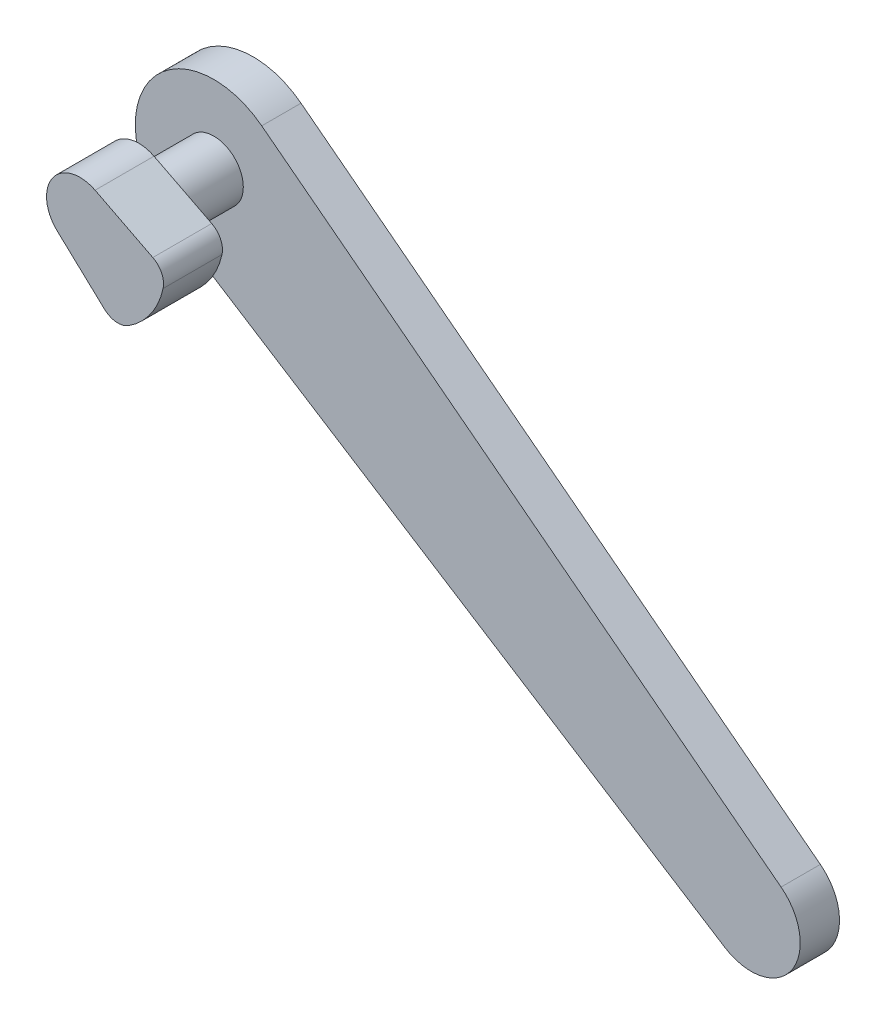
SolidWorks part; units mm, degrees
ref_plane "前视基准面" through (0, 0, 0) normal (0, 0, 1) x (1, 0, 0)
ref_plane "上视基准面" through (0, 0, 0) normal (0, 1, 0) x (1, 0, 0)
ref_plane "右视基准面" through (0, 0, 0) normal (1, 0, 0) x (0, 0, -1)
sketch "草图1" plane through (0, 0, 0) normal (0, 0, 1) x (1, 0, 0)
  line L0 (0.8192, -0.5736) -> (-0.8192, 0.5736) construction
  line L1 (0.8192, -0.5736) -> (3.6313, -2.5427) construction
  line L2 (0.8192, -0.5736) -> (1.4437, -0.5736) construction
  line L3 (-1.9785, -0.6697) -> (0.4349, -2.9203)
  line L4 (-0.0474, 2.0883) -> (2.893, 0.5901)
  line L5 (0, 0) -> (0, 2.9589) construction
  line L6 (0, 0) -> (3.4373, 0) construction
  line L7 (0, 0) -> (0, 3.4623) construction
  arc A0 (-0.0474, 2.0883) -> (-1.9785, -0.6697) centre (-0.8192, 0.5736) ccw
  arc A1 (0.4349, -2.9203) -> (1.6529, -3.0332) centre (1.1169, -2.189) ccw
  arc A2 (1.6529, -3.0332) -> (3.4156, -0.5158) centre (-0.491, 0.3438) ccw
  arc A3 (2.893, 0.5901) -> (3.4156, -0.5158) centre (2.439, -0.3009) cw
  circle A4 centre (0, 0) radius 1.5
  dimension "D4" = 4
  dimension "D5" = 1
  dimension "D7" = 3
  dimension "D8" = 1.7
  dimension "D1" = 35
  dimension "D2" = 2
  dimension "D3" = 8
  dimension "D6" = 3.3
extrude "凸台-拉伸1" add sketch "草图1" along normal blind 3 contours A4 | A3 L4 A0 L3 A1 A2 A4 region at (-2.1455, 1.5023, 0) region at (0, 0, 0)
extrude "凸台-拉伸2" add sketch "草图1<3>" against normal blind 3 contours A4 region at (0, 0, 0)
sketch "草图1<3>" plane through (0, 0, 0) normal (0, 0, 1) x (1, 0, 0) same geometry as "草图1"
sketch "草图2" plane through (0, 0, -3) normal (0, 0, -1) x (-1, 0, 0)
  line L0 (0, 0) -> (-2.7857, -1.9505) construction
  line L1 (-2.7857, -1.9505) -> (-27.3602, -19.1578) construction
  line L2 (-2.4391, 3.1703) -> (-28.8847, -17.1764)
  line L3 (2.1448, -3.3763) -> (-26.0197, -21.268)
  arc A0 (2.1448, -3.3763) -> (-2.4391, 3.1703) centre (0, 0) ccw
  arc A1 (-3.4156, -0.5158) -> (-1.6529, -3.0332) centre (0.491, 0.3438) ccw construction
  arc A2 (-28.8847, -17.1764) -> (-26.0197, -21.268) centre (-27.3602, -19.1578) ccw
  dimension "D1" = 8
  dimension "D2" = 2.5
  dimension "D3" = 30
extrude "凸台-拉伸3" add sketch "草图2" along normal blind 2
